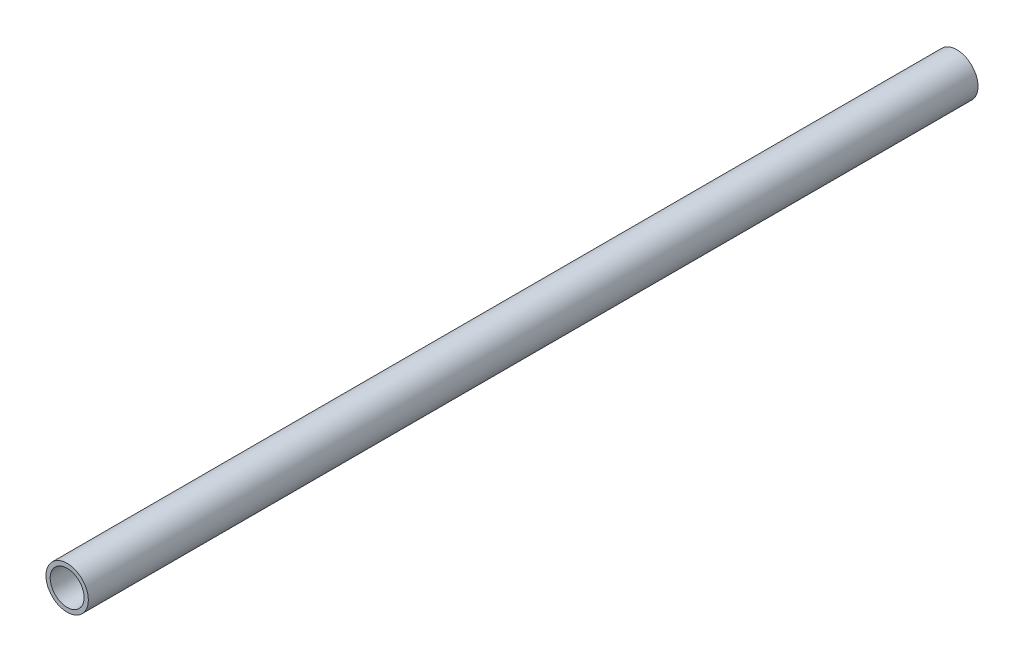
SolidWorks part; units mm, degrees
material "1060 Alloy"
ref_plane "Front Plane" through (0, 0, 0) normal (0, 0, 1) x (1, 0, 0)
ref_plane "Top Plane" through (0, 0, 0) normal (0, 1, 0) x (1, 0, 0)
ref_plane "Right Plane" through (0, 0, 0) normal (1, 0, 0) x (0, 0, -1)
sketch "Sketch1" plane through (0, 0, 0) normal (0, 0, 1) x (1, 0, 0)
  circle A0 centre (0, 0) radius 5
  circle A1 centre (0, 0) radius 4
  dimension "D1" = 10
  dimension "D2" = 8
extrude "body" add sketch "Sketch1" along normal blind 210
